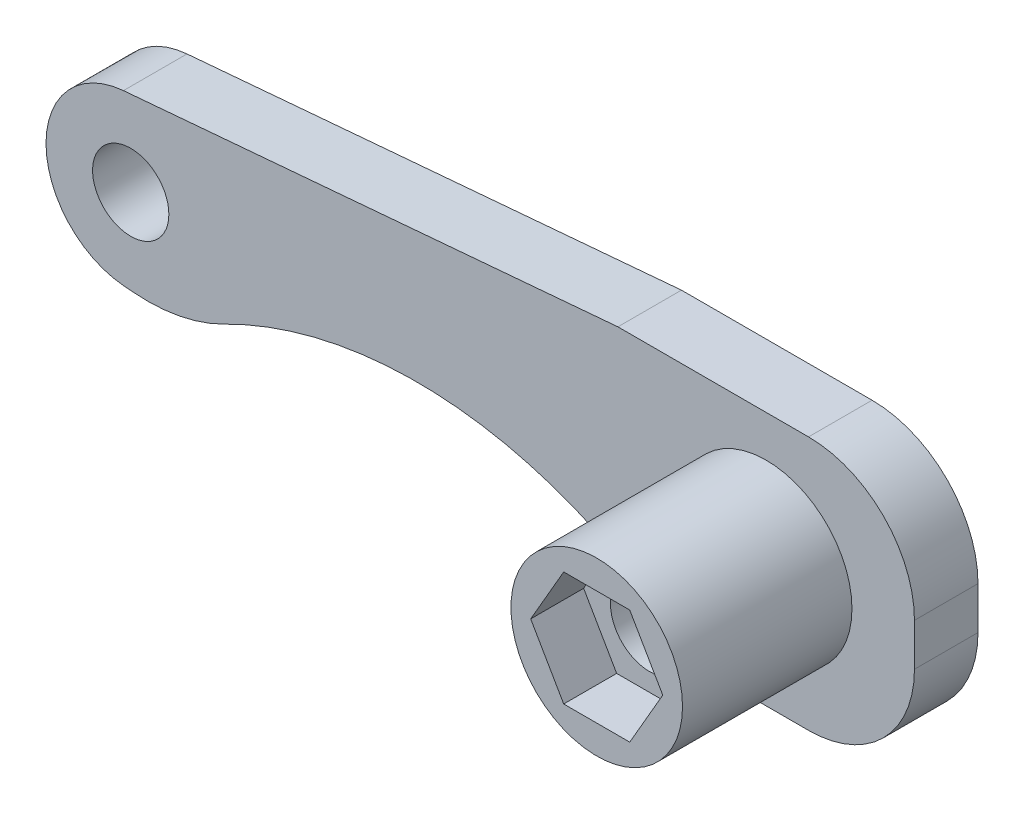
SolidWorks part; units mm, degrees
ref_plane "Front Plane" through (0, 0, 0) normal (0, 0, 1) x (1, 0, 0)
ref_plane "Top Plane" through (0, 0, 0) normal (0, 1, 0) x (1, 0, 0)
ref_plane "Right Plane" through (0, 0, 0) normal (1, 0, 0) x (0, 0, -1)
sketch "Sketch1" plane through (0, 0, 0) normal (0, 0, 1) x (1, 0, 0)
  line L0 (-7, 6) -> (-30.344, 3.9852)
  line L1 (-7, -6) -> (7, -6)
  line L2 (-7, -6) -> (-7, 6)
  line L3 (-7, 6) -> (7, 6)
  line L4 (7, -6) -> (7, 6)
  line L5 (-7, -6) -> (7, 6) construction
  line L6 (-7, 6) -> (7, -6) construction
  line L7 (9.3726, 0) -> (-57.9404, 0) construction
  line L8 (-7, -6) -> (-30.344, -3.9852)
  circle A0 centre (0, 0) radius 4.05
  arc A1 (-30.344, 3.9852) -> (-30.344, -3.9852) centre (-30, 0) ccw
  circle A2 centre (-30, 0) radius 1.8
  point P0 (0, 0)
  dimension "D2" = 8.1
  dimension "D5" = 4
  dimension "D6" = 3.6
  dimension "D1" = 12
  dimension "D3" = 14
  dimension "D4" = 30
extrude "Boss-Extrude1" add sketch "Sketch1" along normal blind 3 contours L1 L4 L3 L2 A0 | L0 A1 L8 L2 region at (-18.6617, 0, 0) region at (0, 5.8156, 0)
extrude "Boss-Extrude2" add sketch "Sketch1<2>" along normal blind 11 contours A0 region at (0, 0, 0)
sketch "Sketch1<2>" plane through (0, 0, 0) normal (0, 0, 1) x (1, 0, 0) same geometry as "Sketch1"
fillet "Fillet1" radius 5 2 edges at (7, -6, 1.5) (7, 6, 1.5)
sketch "Sketch2" plane through (0, 0, 0) normal (0, 0, -1) x (-1, 0, 0)
  circle A0 centre (0, 0) radius 1.85
  dimension "D1" = 3.7
extrude "Cut-Extrude1" cut sketch "Sketch2" against normal through all
sketch "Sketch3" plane through (0, 0, 11) normal (0, 0, 1) x (1, 0, 0)
  line L1 (1.5588, 2.7) -> (-1.5588, 2.7)
  line L2 (-1.5588, 2.7) -> (-3.1177, 0)
  line L3 (-3.1177, 0) -> (-1.5588, -2.7)
  line L4 (-1.5588, -2.7) -> (1.5588, -2.7)
  line L5 (1.5588, -2.7) -> (3.1177, 0)
  line L6 (3.1177, 0) -> (1.5588, 2.7)
  circle A0 centre (0, 0) radius 2.7 construction
  dimension "D1" = 5.4
extrude "Cut-Extrude2" cut sketch "Sketch3" against normal blind 2.5
sketch "Sketch5" plane through (0, 0, 3) normal (0, 0, 1) x (1, 0, 0)
  line L0 (-7, -6) -> (-30.344, -3.9852) construction
  line L1 (-7, -6) -> (2, -6) construction
  line L2 (-7, -6) -> (-3.278, -6)
  line L3 (-7, -6) -> (-27.4109, -4.2383)
  arc A0 (-27.4109, -4.2383) -> (-3.2712, -6) centre (-16.5, -21) cw
  line M5 (-7, -6) -> (2, -6)
  line M12 (-30.344, -3.9852) -> (-7, -6)
  dimension "D1" = 20
  dimension "D2" = 21
  dimension "D3" = 16.5
extrude "Cut-Extrude3" cut sketch "Sketch5" against normal through all and the other way through all contours A0 M12 M5 region at (-15.0974, -3.5677, 3)
fillet "Fillet2" radius 8 2 edges at (-3.2712, -6, 1.5) (-27.4109, -4.2383, 1.5)
